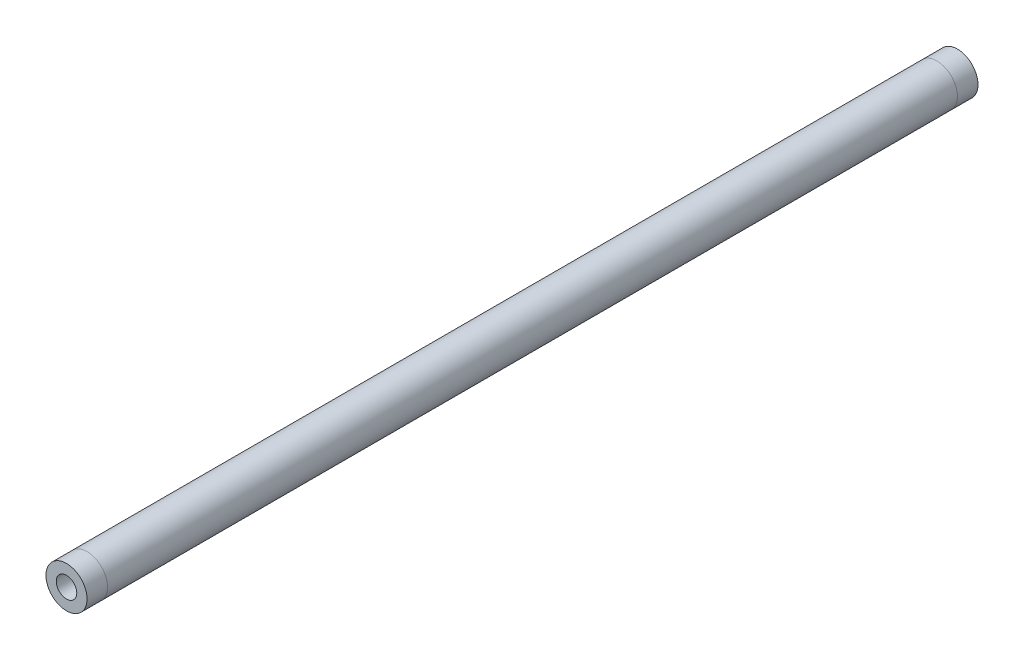
SolidWorks part; units mm, degrees
material "AISI 4130 Steel, annealed at 865C"
ref_plane "Front Plane" through (0, 0, 0) normal (0, 0, 1) x (1, 0, 0)
ref_plane "Top Plane" through (0, 0, 0) normal (0, 1, 0) x (1, 0, 0)
ref_plane "Right Plane" through (0, 0, 0) normal (1, 0, 0) x (0, 0, -1)
sketch "Axis" plane through (0, 0, 0) normal (1, 0, 0) x (0, 0, -1)
  line L0 (0, 0) -> (275.364, 0) construction
  line L1 (275.364, 0) -> (269.014, 0)
  line L2 (275.364, 0) -> (297.2715, 0) construction
  line L3 (0, 0) -> (-21.9075, 0) construction
  point P4 (0, 0)
  point P5 (275.364, 0)
  point P6 (269.014, 0)
  point P8 (297.2715, 0)
  dimension "D1" = 6.35
  dimension "D2" = 21.9075
  dimension "D3" = 21.9075
sketch "Sketch1" plane through (0, 0, 0) normal (0, 0, 1) x (1, 0, 0)
  circle A0 centre (0, 0) radius 6.35
  circle A1 centre (0, 0) radius 5.461
  circle A2 centre (0, 0) radius 3.175
  dimension "D1" = 12.7
  dimension "D2" = 0.889
  dimension "D3" = 6.35
extrude "Threaded insert 1-1" add sketch "Sketch1" against normal blind 6.35 contours A0 A1 | A1 A2 region at (-6.1704, 0, 0) region at (-5.3065, 0, 0)
extrude "Threaded insert 1-2" add sketch "Sketch1<3>" against normal blind 9.525 from surface contours A1 A2 region at (-5.3065, 0, 0) starting at face at (6.35, 0, -6.35)
sketch "Sketch1<3>" plane through (0, 0, 0) normal (0, 0, 1) x (1, 0, 0) same geometry as "Sketch1"
extrude "Tube extrude" add sketch "Sketch1<4>" against normal up to vertex (269.014 mm away) from surface separate body contours A0 A1 region at (-6.1704, 0, 0) up to point (0, 0, -269.014) starting at face at (5.461, 0, -6.35)
sketch "Sketch1<4>" plane through (0, 0, 0) normal (0, 0, 1) x (1, 0, 0) same geometry as "Sketch1"
extrude "Threaded insert 2-1" add sketch "Sketch1<6>" along normal blind 9.525 from surface separate body contours A1 A2 region at (-5.3065, 0, 0) starting at face at (5.461, 0, -269.014)
sketch "Sketch1<6>" plane through (0, 0, 0) normal (0, 0, 1) x (1, 0, 0) same geometry as "Sketch1"
extrude "Threaded insert 2-2" add sketch "Sketch1<9>" against normal blind 6.35 from surface separate body contours A1 A2 | A0 A1 region at (-6.1704, 0, 0) region at (-5.3065, 0, 0) starting at face at (5.461, 0, -269.014)
sketch "Sketch1<9>" plane through (0, 0, 0) normal (0, 0, 1) x (1, 0, 0) same geometry as "Sketch1"
combine bodies "Combine1" operation type add bodies to combine 106 104
equation "\"Threaded insert outer thickness\"= .25"
equation "\"D1@Threaded insert 1-1\"=\"Threaded insert outer thickness\""
equation "\"D1@Threaded insert 2-2\"=\"Threaded insert outer thickness\""
equation "\"D1@Axis\" = \"Threaded insert outer thickness\""
